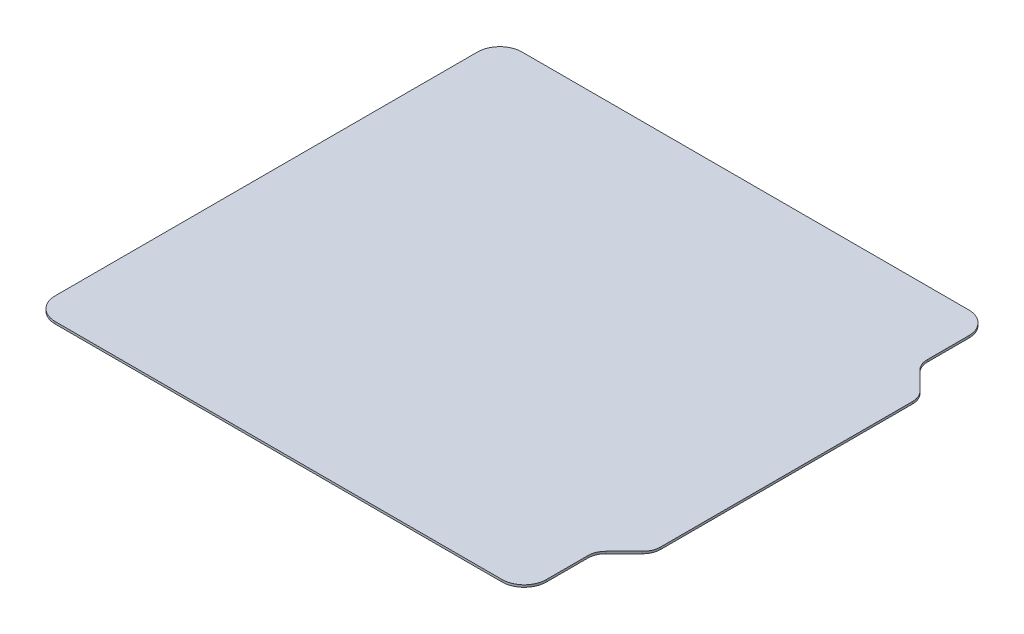
SolidWorks part; units mm, degrees
material "AISI 1020 Steel, Cold Rolled"
ref_plane "Front Plane" through (0, 0, 0) normal (0, 0, 1) x (1, 0, 0)
ref_plane "Top Plane" through (0, 0, 0) normal (0, 1, 0) x (1, 0, 0)
ref_plane "Right Plane" through (0, 0, 0) normal (1, 0, 0) x (0, 0, -1)
sketch "Sketch1" plane through (0, 0, 0) normal (0, 1, 0) x (1, 0, 0)
  line L1 (-117, 105) -> (117, 105)
  line L2 (-117, 105) -> (-117, -105)
  line L3 (-117, -105) -> (117, -105)
  line L4 (117, 105) -> (117, -105)
  line L5 (-117, 105) -> (117, -105) construction
  line L6 (-117, -105) -> (117, 105) construction
  point P0 (0, 0)
  dimension "D1" = 234
  dimension "D2" = 210
extrude "Boss-Extrude1" add sketch "Sketch1" along normal blind 1
sketch "Sketch2" plane through (0, 1, 0) normal (0, 1, 0) x (1, 0, 0)
  line L0 (117, 60) -> (104, 73)
  line L1 (117, -105) -> (117, 105) construction
  line L2 (104, 73) -> (104, 105)
  line L3 (117, 105) -> (-117, 105) construction
  line L4 (104, 105) -> (117, 105)
  line L5 (117, 105) -> (117, 60)
  line L6 (-55, 0) -> (55, 0) construction
  line L7 (104, -105) -> (117, -105)
  line L8 (104, -73) -> (104, -105)
  line L9 (117, -60) -> (104, -73)
  line L10 (117, -105) -> (117, -60)
  dimension "D1" = 45
  dimension "D2" = 32
  dimension "D3" = 13
extrude "Cut-Extrude1" cut sketch "Sketch2" against normal through all
fillet "Fillet1" radius 8 4 edges at (104, 0.5, 73) (117, 0.5, 60) (117, 0.5, -60) (104, 0.5, -73)
fillet "Fillet2" radius 10 4 edges at (-117, 0.5, -105) (-117, 0.5, 105) (104, 0.5, 105) (104, 0.5, -105)
